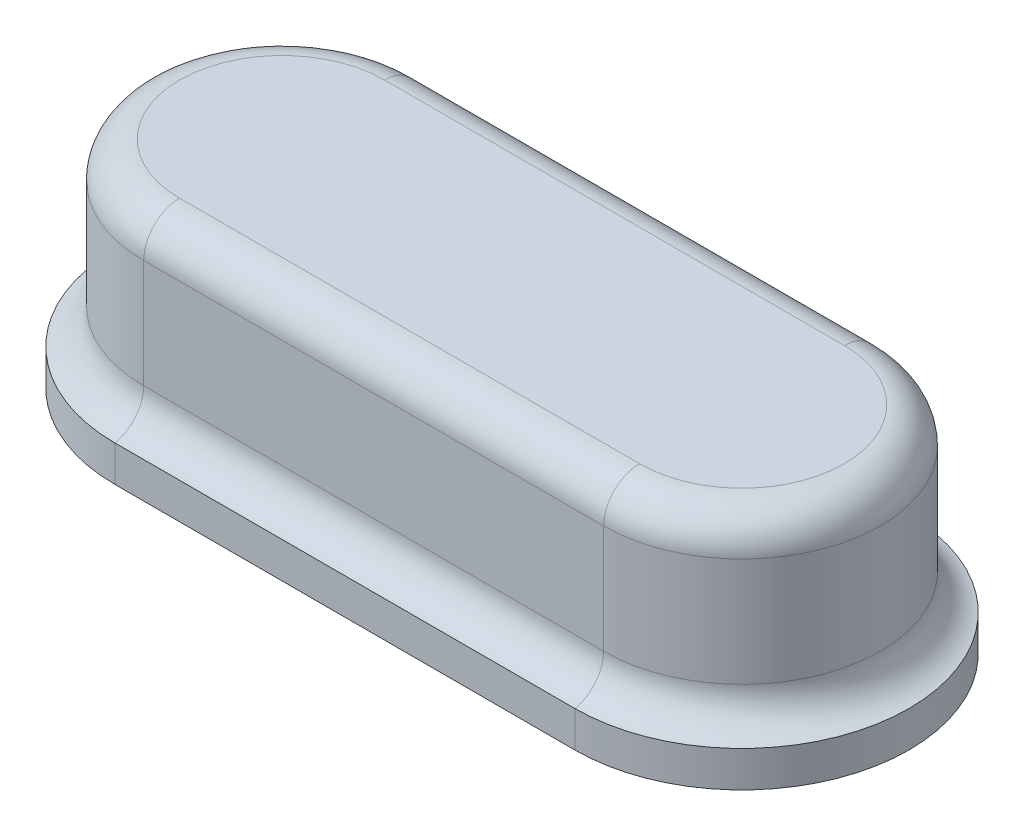
SolidWorks part; units mm, degrees
material "Chrome Stainless Steel"
ref_plane "Front Plane" through (0, 0, 0) normal (0, 0, 1) x (1, 0, 0)
ref_plane "Top Plane" through (0, 0, 0) normal (0, 1, 0) x (1, 0, 0)
ref_plane "Right Plane" through (0, 0, 0) normal (1, 0, 0) x (0, 0, -1)
sketch "Sketch1" plane through (0, 0, 0) normal (0, 1, 0) x (1, 0, 0)
  line L0 (-3.2, 0) -> (3.2, 0) construction
  line L5 (-3.2, 2.325) -> (3.2, 2.325)
  line L6 (-3.2, -2.325) -> (3.2, -2.325)
  arc A0 (-3.2, 2.325) -> (-3.2, -2.325) centre (-3.2, 0) ccw
  arc A1 (3.2, -2.325) -> (3.2, 2.325) centre (3.2, 0) ccw
  point P10 (0, 0)
  dimension "D3" = 4.65
  dimension "D4" = 11.05
extrude "Boss-Extrude1" add sketch "Sketch1" along normal blind 0.5
sketch "Sketch2" plane through (0, 0.5, 0) normal (0, 1, 0) x (1, 0, 0)
  line L4 (-3.2, -1.925) -> (3.2, -1.925)
  line L5 (3.2, 1.925) -> (-3.2, 1.925)
  line L6 (-3.2, -1.925) -> (3.2, -1.925)
  line L7 (3.2, 1.925) -> (-3.2, 1.925)
  arc A4 (-3.2, 1.925) -> (-3.2, -1.925) centre (-3.2, 0) ccw
  arc A5 (3.2, -1.925) -> (3.2, 1.925) centre (3.2, 0) ccw
  arc A6 (-3.2, 1.925) -> (-3.2, -1.925) centre (-3.2, 0) ccw
  arc A7 (3.2, -1.925) -> (3.2, 1.925) centre (3.2, 0) ccw
  dimension "D1" = 0.4
extrude "Boss-Extrude2" add sketch "Sketch2" along normal blind 2.5
fillet "Fillet1" radius 0.5 4 edges at (-5.125, 0.5, 0) (0, 0.5, -1.925) (5.125, 0.5, 0) (0, 0.5, 1.925)
fillet "Fillet3" radius 0.5 4 edges at (0, 3, -1.925) (5.125, 3, 0) (0, 3, 1.925) (-5.125, 3, 0)
